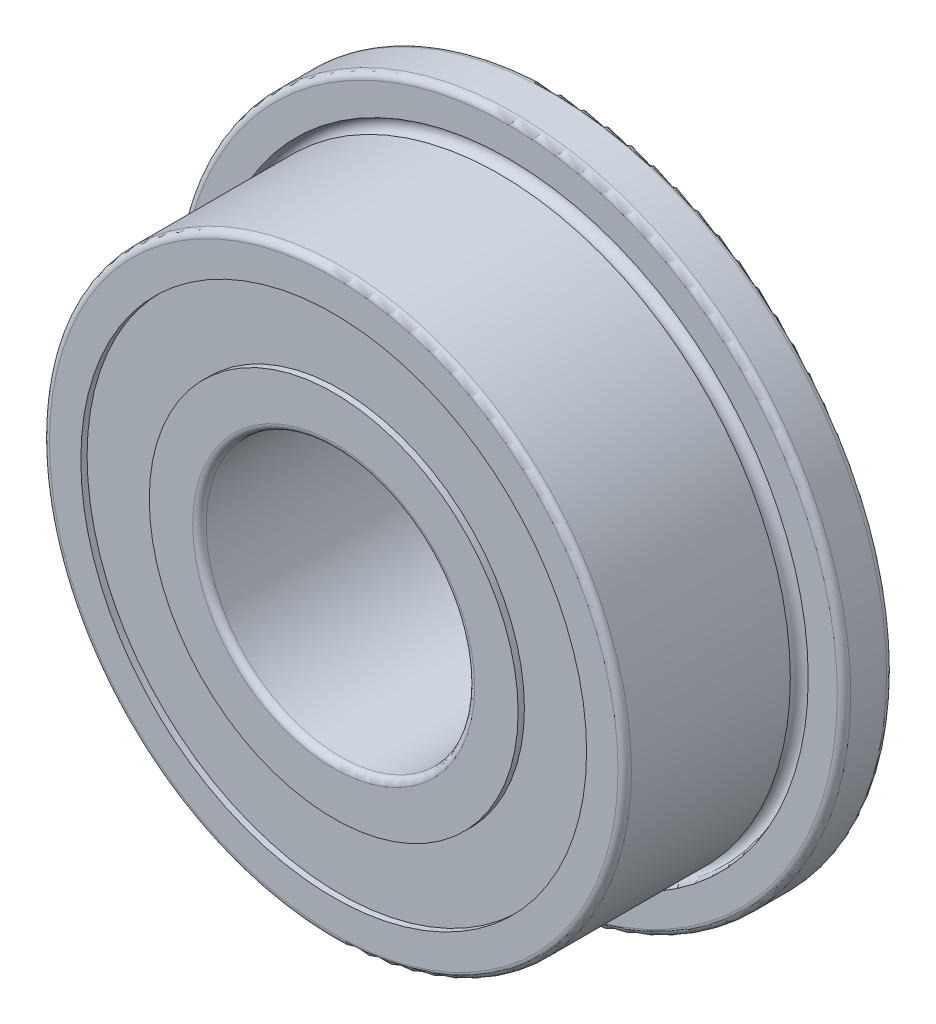
SolidWorks part; units mm, degrees
ref_plane "Plan de face" through (0, 0, 0) normal (0, 0, 1) x (1, 0, 0)
ref_plane "Plan de dessus" through (0, 0, 0) normal (0, 1, 0) x (1, 0, 0)
ref_plane "Plan de droite" through (0, 0, 0) normal (1, 0, 0) x (0, 0, -1)
ref_plane "Plan1" through (0, 0, 0) normal (1, 0, 0) x (0, 0, -1)
sketch "Esquisse1" plane through (0, 0, 0) normal (1, 0, 0) x (0, 0, -1)
  line L0 (0, 6.35) -> (0, 5.649)
  line L1 (0, 5.649) -> (0.14, 5.649)
  line L2 (0.14, 5.649) -> (0.14, 4.12)
  line L3 (0.14, 4.12) -> (0, 4.12)
  line L4 (0, 4.12) -> (0, 3.15)
  line L5 (0.15, 3) -> (4.85, 3)
  line L6 (5, 3.15) -> (5, 4.12)
  line L7 (5, 4.12) -> (4.86, 4.12)
  line L8 (4.86, 4.12) -> (4.86, 5.649)
  line L9 (4.86, 5.649) -> (5, 5.649)
  line L10 (5, 5.649) -> (5, 7.35)
  line L11 (4.85, 7.5) -> (4.05, 7.5)
  line L12 (3.9, 7.35) -> (3.9, 6.7)
  line L13 (3.7, 6.5) -> (0.15, 6.5)
  line L14 (5, 0) -> (0, 0) construction
  arc A0 (0, 3.15) -> (0.15, 3) centre (0.15, 3.15) ccw
  arc A1 (4.85, 3) -> (5, 3.15) centre (4.85, 3.15) ccw
  arc A2 (5, 7.35) -> (4.85, 7.5) centre (4.85, 7.35) ccw
  arc A3 (4.05, 7.5) -> (3.9, 7.35) centre (4.05, 7.35) ccw
  arc A4 (3.9, 6.7) -> (3.7, 6.5) centre (3.9, 6.5) cw
  arc A5 (0.15, 6.5) -> (0, 6.35) centre (0.15, 6.35) ccw
revolve "Révolution1" add sketch "Esquisse1" angle 360 about L14 reverse direction yes
